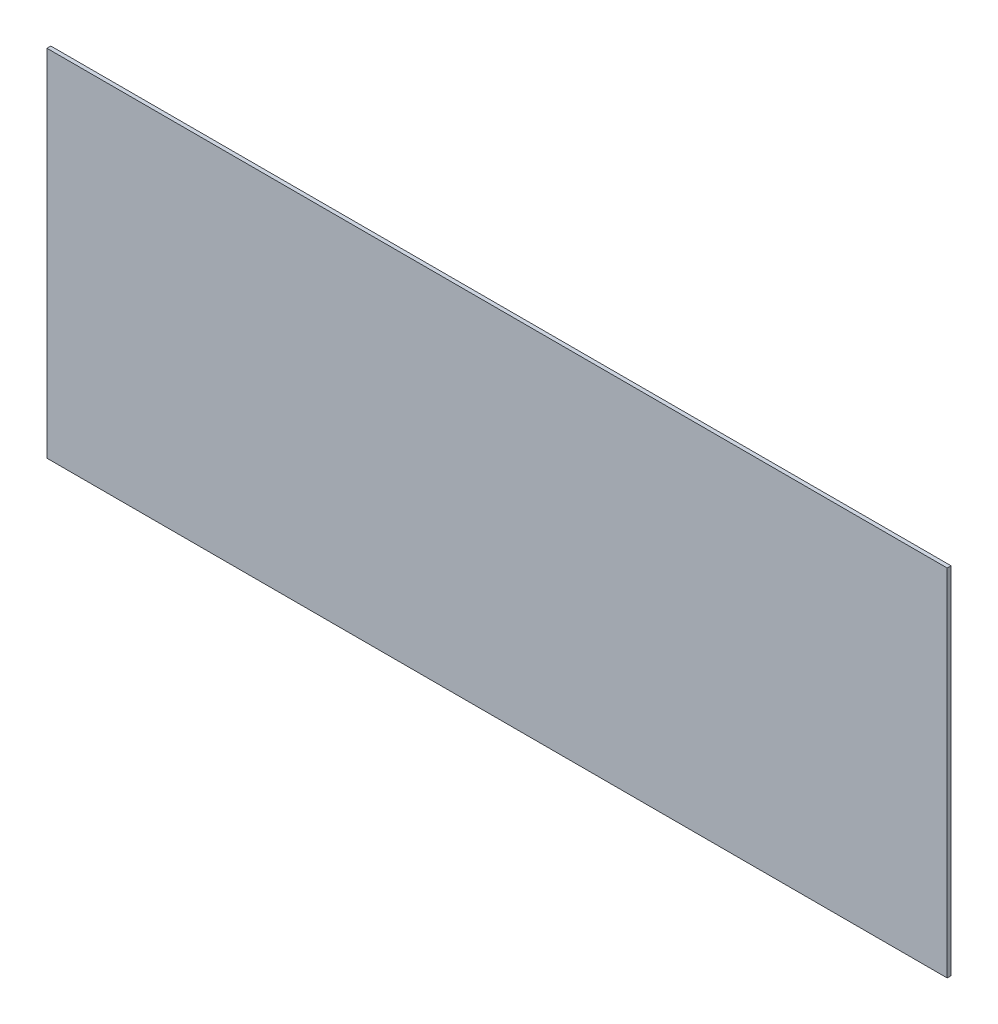
SolidWorks part; units mm, degrees
material "ABS PC"
ref_plane "Front Plane" through (0, 0, 0) normal (0, 0, 1) x (1, 0, 0)
ref_plane "Top Plane" through (0, 0, 0) normal (0, 1, 0) x (1, 0, 0)
ref_plane "Right Plane" through (0, 0, 0) normal (1, 0, 0) x (0, 0, -1)
sketch "Sketch1" plane through (0, 0, 0) normal (0, 0, 1) x (1, 0, 0)
  line L1 (0, 0) -> (736.6, 0)
  line L2 (0, 0) -> (0, -290.5125)
  line L3 (0, -290.5125) -> (736.6, -290.5125)
  line L4 (736.6, 0) -> (736.6, -290.5125)
  dimension "D1" = 290.5125
  dimension "D2" = 736.6
extrude "Boss-Extrude1" add sketch "Sketch1" along normal blind 3.175
